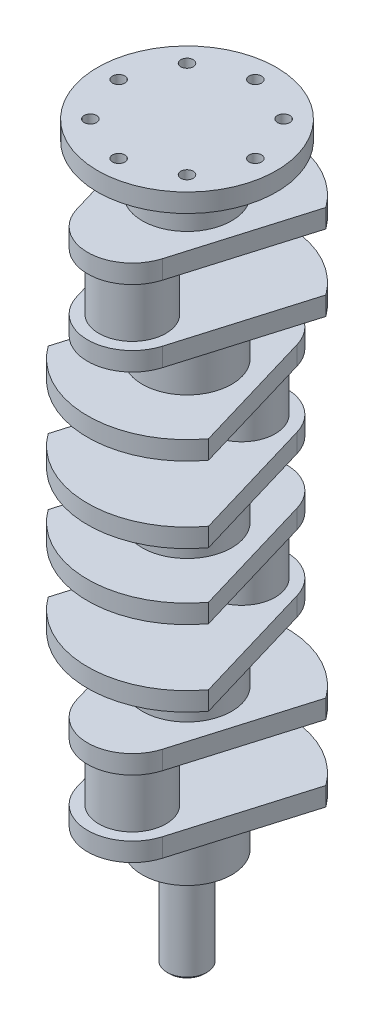
SolidWorks part; units mm, degrees
note: The reader was unsure of these and kept them because the rebuilt part matched: shared geometry of "Sketch1<3>", "Sketch2<3>".
ref_plane "Front Plane" through (0, 0, 0) normal (0, 0, 1) x (1, 0, 0)
ref_plane "Top Plane" through (0, 0, 0) normal (0, 1, 0) x (1, 0, 0)
ref_plane "Right Plane" through (0, 0, 0) normal (1, 0, 0) x (0, 0, -1)
sketch "Sketch1" plane through (0, 0, 0) normal (0, 1, 0) x (1, 0, 0)
  circle A0 centre (0, 0) radius 16
  circle A1 centre (0, 0) radius 36
extrude "Boss-Extrude1" add sketch "Sketch1" along normal blind 80 contours A0
extrude "Boss-Extrude2" add sketch "Sketch1<3>" along normal blind 38 from offset 80 contours A1 A0 | A0
sketch "Sketch1<3>" plane through (0, 0, 0) normal (0, 1, 0) x (1, 0, 0) same geometry as "Sketch1"
sketch "Sketch2" plane through (0, 118, 0) normal (0, 1, 0) x (1, 0, 0)
  line L1 (-34.5175, -54.2246) -> (-64.5699, 47.2306)
  line L2 (34.5175, -54.2246) -> (64.5699, 47.2306)
  circle A0 centre (0, -44) radius 27
  arc A1 (-34.5175, -54.2246) -> (34.5175, -54.2246) centre (0, -44) ccw
  arc A3 (64.5699, 47.2306) -> (-64.5699, 47.2306) centre (0, 0) ccw
  circle M4 centre (0, 0) radius 36
  dimension "D1" = 33
extrude "Boss-Extrude3" add sketch "Sketch2" along normal blind 15 contours A0 M4 | A0 M4 | L2 A3 L1 A1 A0 M4 | A0 M4
extrude "Boss-Extrude4" add sketch "Sketch2<3>" along normal blind 61 contours A0 M4 | A0 M4
sketch "Sketch2<3>" plane through (0, 118, 0) normal (0, 1, 0) x (1, 0, 0) same geometry as "Sketch2"
pattern_linear "LPattern1" count 2 spacing 61 along (0, 1, 0) of "Boss-Extrude3"
sketch "Sketch3" plane through (0, 194, 0) normal (0, 1, 0) x (1, 0, 0)
  circle A0 centre (0, 0) radius 36
extrude "Boss-Extrude5" add sketch "Sketch3" along normal blind 38
sketch "Sketch5" plane through (0, 194, 0) normal (0, 1, 0) x (1, 0, 0)
  line L1 (-34.5175, 54.2246) -> (-64.5699, -47.2306)
  line L6 (64.5699, -47.2306) -> (34.5175, 54.2246)
  arc A0 (64.5699, -47.2306) -> (-64.5699, -47.2306) centre (0, 0) cw
  arc A1 (-34.5175, 54.2246) -> (34.5175, 54.2246) centre (0, 44) cw
extrude "Boss-Extrude6" add sketch "Sketch5" along normal blind 15 from offset 38
sketch "Sketch6" plane through (0, 247, 0) normal (0, 1, 0) x (1, 0, 0)
  line L0 (0, 0) -> (0, 44)
  circle A1 centre (0, 44) radius 27
extrude "Boss-Extrude8" add sketch "Sketch6" along normal blind 46
pattern_linear "LPattern3" count 2 spacing 61 along (0, 1, 0) of "Boss-Extrude6"
pattern_linear "LPattern5" count 2 spacing 114 along (0, 1, 0) of "Boss-Extrude5", "Boss-Extrude6", "LPattern3", "Boss-Extrude8"
pattern_linear "LPattern6" count 2 spacing 342 along (0, 1, 0) of "Boss-Extrude2", "Boss-Extrude3", "Boss-Extrude4", "LPattern1"
sketch "Sketch7" plane through (0, 536, 0) normal (0, 1, 0) x (1, 0, 0)
  circle A0 centre (0, 0) radius 36
extrude "Boss-Extrude9" add sketch "Sketch7" along normal blind 38
sketch "Sketch8" plane through (0, 574, 0) normal (0, 1, 0) x (1, 0, 0)
  circle A1 centre (0, 0) radius 72
  circle A2 centre (0, 55) radius 5
  circle A3 centre (38.8909, 38.8909) radius 5
  circle A4 centre (55, 0) radius 5
  circle A5 centre (38.8909, -38.8909) radius 5
  circle A6 centre (0, -55) radius 5
  circle A7 centre (-38.8909, -38.8909) radius 5
  circle A8 centre (-55, 0) radius 5
  circle A9 centre (-38.8909, 38.8909) radius 5
  point P22 (0, 0)
  dimension "D1" = 8
extrude "Boss-Extrude10" add sketch "Sketch8" along normal blind 15
chamfer "Chamfer1" distance 2 angle 45 1 edges at (0, 0, 16)
fillet "Fillet1" radius 3 1 edges at (0, 80, 16)
